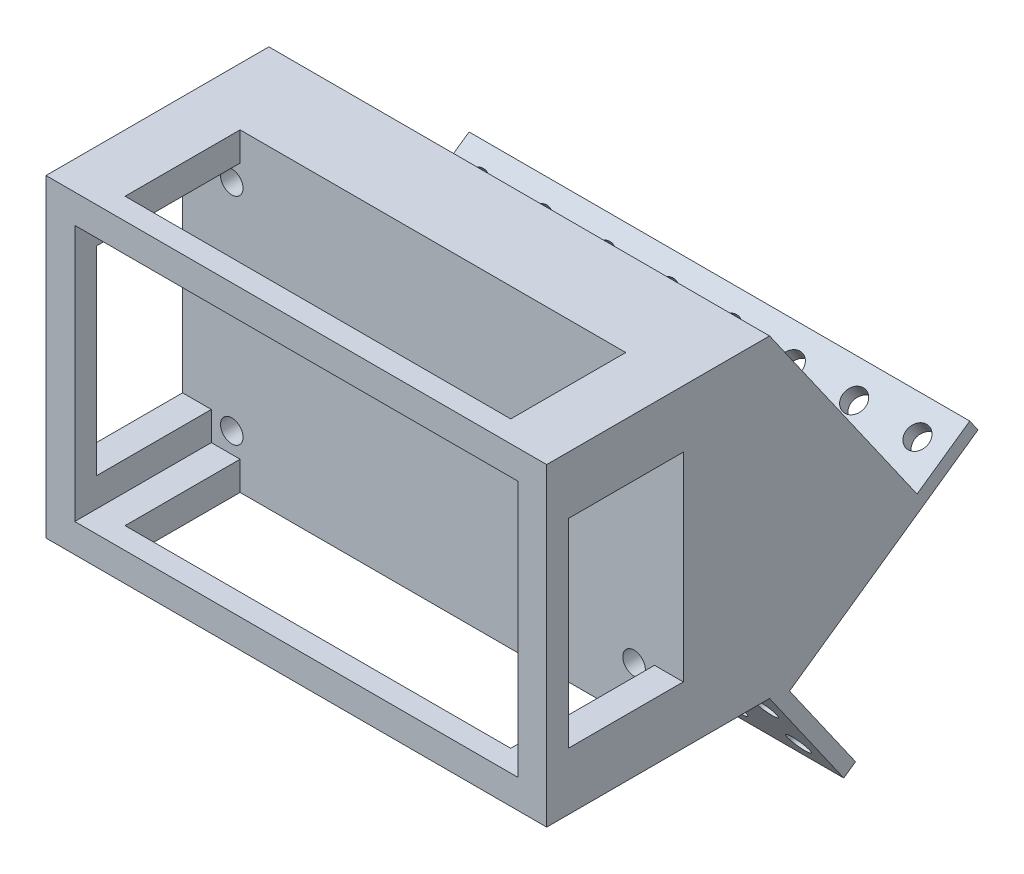
SolidWorks part; units mm, degrees
ref_plane "Front Plane" through (0, 0, 0) normal (0, 0, 1) x (1, 0, 0)
ref_plane "Top Plane" through (0, 0, 0) normal (0, 1, 0) x (1, 0, 0)
ref_plane "Right Plane" through (0, 0, 0) normal (1, 0, 0) x (0, 0, -1)
sketch "Sketch1" plane through (0, 0, 0) normal (0, 0, 1) x (1, 0, 0)
  line L0 (-44.4246, 23.8125) -> (-44.4246, -23.8125) construction
  line L1 (-48.9331, -28.321) -> (48.9331, -28.321)
  line L2 (-48.9331, -28.321) -> (-48.9331, 28.321)
  line L3 (-48.9331, 28.321) -> (48.9331, 28.321)
  line L4 (48.9331, -28.321) -> (48.9331, 28.321)
  line L5 (-48.9331, -28.321) -> (48.9331, 28.321) construction
  line L6 (-48.9331, 28.321) -> (48.9331, -28.321) construction
  line L7 (-55.2831, -34.671) -> (55.2831, -34.671)
  line L8 (-55.2831, -34.671) -> (-55.2831, 34.671)
  line L9 (-55.2831, 34.671) -> (55.2831, 34.671)
  line L10 (55.2831, -34.671) -> (55.2831, 34.671)
  line L11 (-55.2831, -34.671) -> (55.2831, 34.671) construction
  line L12 (-55.2831, 34.671) -> (55.2831, -34.671) construction
  line L13 (0, 28.321) -> (0, -28.321) construction
  line L14 (-55.2831, -21.971) -> (-48.9331, -21.971)
  line L15 (-48.9331, -21.971) -> (-48.9331, -28.321)
  line L16 (-48.9331, -28.321) -> (-42.5831, -28.321)
  line L17 (-42.5831, -28.321) -> (-42.5831, -34.671)
  line L18 (42.5831, -28.321) -> (42.5831, -34.671)
  line L19 (48.9331, -28.321) -> (42.5831, -28.321)
  line L20 (48.9331, -21.971) -> (48.9331, -28.321)
  line L21 (55.2831, -21.971) -> (48.9331, -21.971)
  line L22 (-55.2831, 0) -> (55.2831, 0) construction
  line L23 (55.2831, 21.971) -> (48.9331, 21.971)
  line L24 (48.9331, 21.971) -> (48.9331, 28.321)
  line L25 (48.9331, 28.321) -> (42.5831, 28.321)
  line L26 (42.5831, 28.321) -> (42.5831, 34.671)
  line L27 (-42.5831, 28.321) -> (-42.5831, 34.671)
  line L28 (-48.9331, 28.321) -> (-42.5831, 28.321)
  line L29 (-48.9331, 21.971) -> (-48.9331, 28.321)
  line L30 (-55.2831, 21.971) -> (-48.9331, 21.971)
  circle A0 centre (-44.4246, -23.8125) radius 2.4892
  circle A1 centre (-44.4246, 23.8125) radius 2.4892
  circle A2 centre (44.4246, -23.8125) radius 2.4892
  circle A3 centre (44.4246, 23.8125) radius 2.4892
  point P0 (0, 0)
  point P6 (0, 0)
  point P11 (-48.9331, 0)
  point P16 (-44.4246, 0)
  dimension "D5" = 4.9784
  dimension "D1" = 97.8662
  dimension "D2" = 56.642
  dimension "D3" = 6.35
  dimension "D4" = 6.35
  dimension "D6" = 4.5085
  dimension "D7" = 12.7
  dimension "D8" = 47.625
  dimension "D9" = 12.7
extrude "Boss-Extrude1" add sketch "Sketch1" along normal mid plane 19.05 contours L30 L8 L14 L15 L16 L17 L7 L18 L19 L20 L21 L10 L23 L24 L25 L26 L9 L27 L28 L29 A2 A1 A0 A3 | L8 L30 L29 L28 L27 L9 | L26 L25 L24 L23 L10 L9 | L10 L21 L20 L19 L18 L7 | L17 L16 L15 L14 L8 L7 | L30 L8 L14 L2 | L27 L3 L26 L9 | L10 L23 L4 L21 | L18 L1 L17 L7 region at (0, 0, 0) region at (-49.9914, -29.3793, 0) region at (0, -31.496, 0) region at (-52.1081, 0, 0) region at (49.9914, -29.3793, 0) region at (-49.9914, 29.3793, 0) region at (52.1081, 0, 0) region at (0, 31.496, 0) region at (49.9914, 29.3793, 0)
extrude "Boss-Extrude2" add sketch "Sketch1<3>" along normal blind 34.925 contours L8 L30 L29 L28 L27 L9 | L26 L25 L24 L23 L10 L9 | L17 L16 L15 L14 L8 L7 | L10 L21 L20 L19 L18 L7 region at (-49.9914, -29.3793, 0) region at (49.9914, -29.3793, 0) region at (-49.9914, 29.3793, 0) region at (49.9914, 29.3793, 0)
sketch "Sketch1<3>" plane through (0, 0, 0) normal (0, 0, 1) x (1, 0, 0) same geometry as "Sketch1"
extrude "Boss-Extrude3" add sketch "Sketch1<5>" along normal blind 4.7625 from surface contours L27 L3 L26 L9 | L26 L3 L4 L23 L10 L9 | L10 L23 L4 L21 | L10 L21 L4 L1 L18 L7 | L18 L1 L17 L7 | L17 L1 L2 L14 L8 L7 | L30 L8 L14 L2 | L8 L30 L2 L3 L27 L9 region at (-49.9914, -29.3793, 0) region at (0, -31.496, 0) region at (-52.1081, 0, 0) region at (49.9914, -29.3793, 0) region at (-49.9914, 29.3793, 0) region at (52.1081, 0, 0) region at (0, 31.496, 0) region at (49.9914, 29.3793, 0) starting at face at (-48.9331, 28.321, 34.925)
sketch "Sketch1<5>" plane through (0, 0, 0) normal (0, 0, 1) x (1, 0, 0) same geometry as "Sketch1"
sketch "Sketch2" plane through (0, 0, 0) normal (1, 0, 0) x (0, 0, -1)
  line L0 (9.525, 34.671) -> (9.525, -34.671)
  line L1 (9.525, -34.671) -> (9.525, 34.671) construction
  line L2 (9.525, 34.671) -> (42.1051, -11.8582)
  line L3 (55.5598, -6.313) -> (13.9469, -35.4507)
  line L4 (9.525, -34.671) -> (25.9149, -58.0783)
  line L5 (25.9149, -58.0783) -> (28.5158, -56.2572)
  line L6 (28.5158, -56.2572) -> (13.9469, -35.4507)
  line L8 (55.5598, -6.313) -> (53.7387, -3.7122)
  line L9 (53.7387, -3.7122) -> (42.1051, -11.8582)
  point P6 (62.9115, 2.7107)
  point P9 (0, 0)
  point P13 (64.2035, 0.1099)
  point P14 (66.3926, 1.2721)
  dimension "D1" = 3.175
  dimension "D2" = 55
  dimension "D3" = 25.4
  dimension "D4" = 3.175
  dimension "D5" = 50.8
extrude "Boss-Extrude4" add sketch "Sketch2" along normal up to surface (55.2831 mm away) and the other way up to surface (55.2831 mm away) up to face at (55.2831, 0, 15.0813) other way up to face at (-55.2831, 0, 15.0813)
sketch "Sketch3" plane through (0, -6.9311, 9.8987) normal (0, -0.5736, 0.8192) x (1, 0, 0)
  line L0 (-55.2831, -33.8641) -> (-55.2831, -62.4391) construction
  line L1 (55.2831, -62.4391) -> (-55.2831, -62.4391) construction
  line L2 (55.2831, -62.4391) -> (55.2831, -33.8641) construction
  circle A0 centre (-48.9331, -56.0891) radius 2.4892
  circle A1 centre (-34.9522, -56.0891) radius 2.4892
  circle A2 centre (-20.9713, -56.0891) radius 2.4892
  circle A3 centre (-6.9904, -56.0891) radius 2.4892
  circle A4 centre (6.9904, -56.0891) radius 2.4892
  circle A5 centre (20.9713, -56.0891) radius 2.4892
  circle A6 centre (34.9522, -56.0891) radius 2.4892
  circle A7 centre (48.9331, -56.0891) radius 2.4892
  circle A8 centre (-34.9522, -43.3891) radius 2.4892
  circle A9 centre (-20.9713, -43.3891) radius 2.4892
  circle A10 centre (-6.9904, -43.3891) radius 2.4892
  circle A11 centre (6.9904, -43.3891) radius 2.4892
  circle A12 centre (20.9713, -43.3891) radius 2.4892
  circle A13 centre (34.9522, -43.3891) radius 2.4892
  circle A14 centre (48.9331, -43.3891) radius 2.4892
  circle A15 centre (-48.9331, -43.3891) radius 2.4892
  point P8 (-48.9331, -43.3891)
  dimension "D3" = 4.9784
  dimension "D1" = 6.35
  dimension "D2" = 6.35
  dimension "D6" = 6.35
  dimension "D7" = 12.7
  dimension "D4" = 8
  dimension "D5" = 2
extrude "Cut-Extrude1" cut sketch "Sketch3" against normal through all both
sketch "Sketch4" plane through (0, -27.7399, -19.4237) normal (0, 0.8192, 0.5736) x (1, 0, 0)
  line L0 (55.2831, 41.891) -> (-55.2831, 41.891) construction
  line L1 (55.2831, 27.6889) -> (55.2831, 41.891) construction
  line L2 (-55.2831, 41.891) -> (-55.2831, 27.6889) construction
  circle A0 centre (48.9331, 35.541) radius 2.4892
  circle A1 centre (34.9522, 35.541) radius 2.4892
  circle A2 centre (20.9713, 35.541) radius 2.4892
  circle A3 centre (6.9904, 35.541) radius 2.4892
  circle A4 centre (-6.9904, 35.541) radius 2.4892
  circle A5 centre (-20.9713, 35.541) radius 2.4892
  circle A6 centre (-34.9522, 35.541) radius 2.4892
  circle A7 centre (-48.9331, 35.541) radius 2.4892
  dimension "D5" = 4.9784
  dimension "D1" = 6.35
  dimension "D2" = 6.35
  dimension "D4" = 6.35
  dimension "D3" = 8
extrude "Cut-Extrude2" cut sketch "Sketch4" against normal through all both
